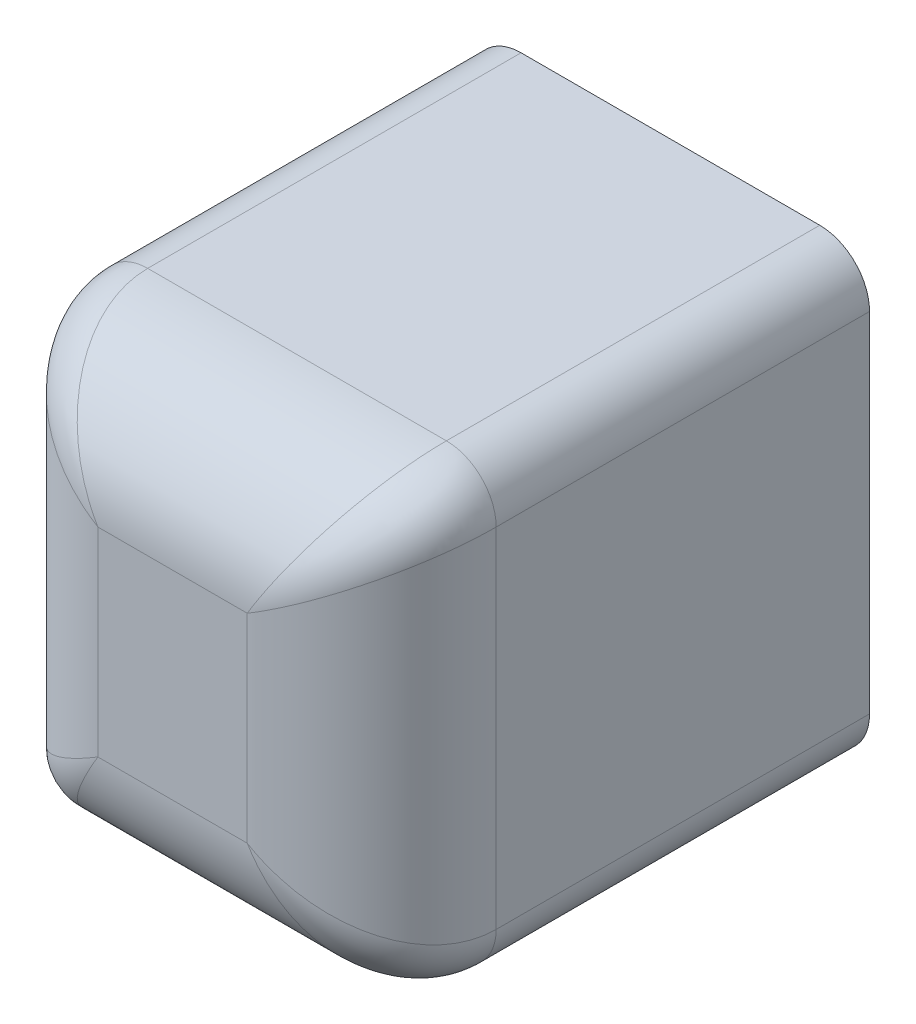
SolidWorks part; units mm, degrees
material "Commercially Pure Grade 2 Textured (SS)"
ref_plane "Front Plane" through (0, 0, 0) normal (0, 0, 1) x (1, 0, 0)
ref_plane "Top Plane" through (0, 0, 0) normal (0, 1, 0) x (1, 0, 0)
ref_plane "Right Plane" through (0, 0, 0) normal (1, 0, 0) x (0, 0, -1)
sketch "Sketch1" plane through (0, 0, 0) normal (0, 0, 1) x (1, 0, 0)
  line L1 (-80, -90) -> (80, -90)
  line L2 (-80, -90) -> (-80, 90)
  line L3 (-80, 90) -> (80, 90)
  line L4 (80, -90) -> (80, 90)
  line L5 (-80, -90) -> (80, 90) construction
  line L6 (-80, 90) -> (80, -90) construction
  point P0 (0, 0)
  dimension "D1" = 180
  dimension "D2" = 160
extrude "Boss-Extrude1" add sketch "Sketch1" along normal blind 200
fillet "Fillet1" radius 50 4 edges at (0, -90, 200) (-80, 0, 200) (0, 90, 200) (80, 0, 200)
fillet "Fillet2" radius 20 8 edges at (-65.3553, -75.3553, 185.3553) (65.3553, -75.3553, 185.3553) (65.3553, 75.3553, 185.3553) (-65.3553, 75.3553, 185.3553) (-80, -90, 75) (80, -90, 75) (80, 90, 75) (-80, 90, 75)
